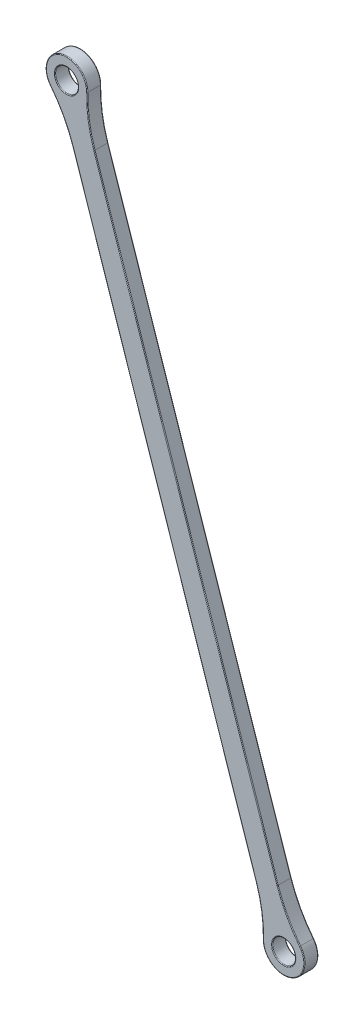
SolidWorks part; units mm, degrees
ref_plane "前视基准面" through (0, 0, 0) normal (0, 0, 1) x (1, 0, 0)
ref_plane "上视基准面" through (0, 0, 0) normal (0, 1, 0) x (1, 0, 0)
ref_plane "右视基准面" through (0, 0, 0) normal (1, 0, 0) x (0, 0, -1)
sketch "草图1" plane through (0, 0, 0) normal (0, 0, 1) x (1, 0, 0)
  line L0 (14.5, 81.5) -> (-32.6652, 221.7835) construction
  line L1 (14.5, 81.5) -> (-32.6652, 221.7835) construction
  line L2 (14.5, 81.5) -> (-32.6652, 221.7835) construction
  line L3 (12.1303, 80.7033) -> (-35.0348, 220.9867)
  line L4 (16.8697, 82.2967) -> (-30.2955, 222.5802)
  circle A0 centre (-32.6652, 221.7835) radius 4.5 construction
  circle A1 centre (14.5, 81.5) radius 4.5 construction
  arc A2 (12.1303, 80.7033) -> (16.8697, 82.2967) centre (14.5, 81.5) ccw
  arc A3 (-30.2955, 222.5802) -> (-35.0348, 220.9867) centre (-32.6652, 221.7835) ccw
  arc A4 (-30.2955, 222.5802) -> (-35.0348, 220.9867) centre (-32.6652, 221.7835) cw
  arc A5 (16.8697, 82.2967) -> (12.1303, 80.7033) centre (14.5, 81.5) ccw
  arc A6 (-29.1031, 219.0336) -> (-33.8424, 217.4402) centre (-32.6652, 221.7835) ccw
  arc A7 (10.9379, 84.2499) -> (15.6772, 85.8433) centre (14.5, 81.5) ccw
  point P5 (-9.0826, 151.6417)
  dimension "D1" = 9
  dimension "D2" = 9
  dimension "D3" = 5
extrude "凸台-拉伸1" add sketch "草图1" against normal blind 3 contours L3 A7 L4 A2 | A5 L4 A4 L3 | L4 A6 L3 A3 region at (15.3369, 79.0107, 0) region at (-9.0826, 151.6417, 0) region at (-34.059, 225.9292, 0)
fillet "圆角1" radius 30 4 edges at (10.9379, 84.2499, -1.5) (15.6772, 85.8433, -1.5) (-29.1031, 219.0336, -1.5) (-33.8424, 217.4402, -1.5)
fillet "圆角2" radius 0.15 20 edges at (17, 81.5, -3) (-33.3886, 214.7161, -3) (-34.0992, 226.0488, -3) (-27.819, 216.5887, -3) (-6.7129, 152.4384, -3) (15.2235, 88.5673, -3) (15.9341, 77.2346, -3) (9.6539, 86.6948, -3) (-11.4522, 150.845, -3) (-30.1652, 221.7835, -3) (17, 81.5, 0) (15.2235, 88.5673, 0) (-6.7129, 152.4384, 0) (-27.819, 216.5887, 0) (-34.0992, 226.0488, 0) (-33.3886, 214.7161, 0) (-11.4522, 150.845, 0) (9.6539, 86.6948, 0) (15.9341, 77.2346, 0) (-30.1652, 221.7835, 0)
